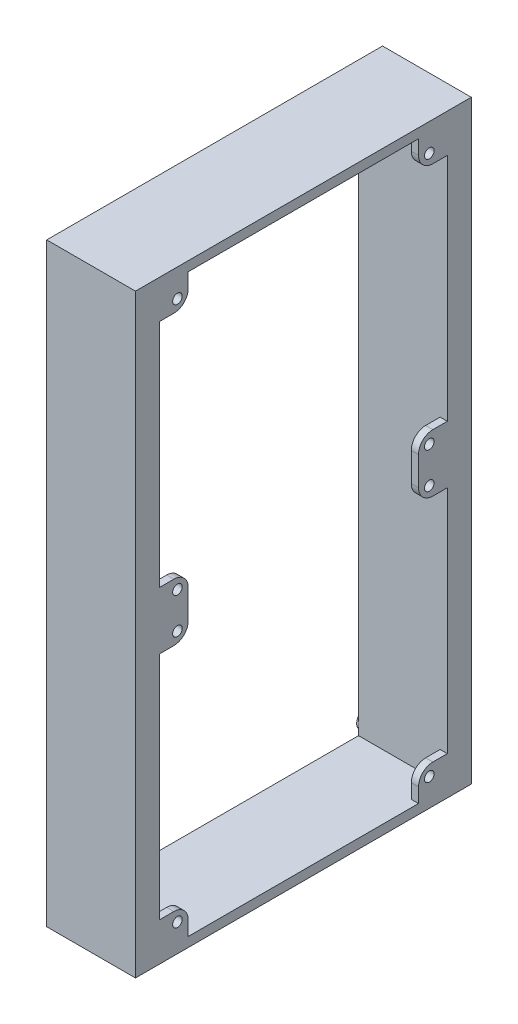
SolidWorks part; units mm, degrees
ref_plane "Front Plane" through (0, 0, 0) normal (1, 0, 0) x (0, 1, 0)
ref_plane "Top Plane" through (0, 0, 0) normal (0, 0, 1) x (0, 1, 0)
ref_plane "Right Plane" through (0, 0, 0) normal (0, 1, 0) x (-1, 0, 0)
sketch "Sketch1" plane through (0, 0, 0) normal (1, 0, 0) x (0, 1, 0)
  line L0 (0, 60) -> (0, -60) construction
  line L1 (-120, -60) -> (120, -60)
  line L2 (-120, -60) -> (-120, 60)
  line L3 (-120, 60) -> (120, 60)
  line L4 (120, -60) -> (120, 60)
  line L5 (-120, -60) -> (120, 60) construction
  line L6 (-120, 60) -> (120, -60) construction
  line L7 (0, 60) -> (0, -60.0055) construction
  line L8 (-120, -60) -> (0, 60) construction
  line L9 (-12, 60) -> (0, 60)
  line L10 (-120, 48) -> (-114, 48)
  line L11 (-120, 48) -> (-120, 60)
  line L12 (-120, 60) -> (-108, 60)
  line L13 (-108, 54) -> (-108, 60)
  line L14 (-12, 60) -> (-12, 54)
  line L15 (-6, 48) -> (0, 48)
  line L16 (0, 60) -> (0, 48)
  line L17 (0, -48) -> (0, -60)
  line L18 (0, -48) -> (-6, -48)
  line L19 (-12, -54) -> (-12, -60)
  line L20 (0, -60) -> (-12, -60)
  line L21 (-108, -60) -> (-120, -60)
  line L22 (-108, -60) -> (-108, -54)
  line L23 (-114, -48) -> (-120, -48)
  line L24 (-120, -60) -> (-120, -48)
  line L25 (0, 48) -> (0, 60)
  line L26 (0, 48) -> (6, 48)
  line L27 (12, 54) -> (12, 60)
  line L28 (0, 60) -> (12, 60)
  line L29 (12, -60) -> (0, -60)
  line L30 (0, -60) -> (0, -48)
  line L31 (6, -48) -> (0, -48)
  line L32 (12, -60) -> (12, -54)
  line L33 (120, -48) -> (120, -60)
  line L34 (120, -60) -> (108, -60)
  line L35 (108, -54) -> (108, -60)
  line L36 (120, -48) -> (114, -48)
  line L37 (108, 60) -> (120, 60)
  line L38 (120, 60) -> (120, 48)
  line L39 (114, 48) -> (120, 48)
  line L40 (108, 60) -> (108, 54)
  line L59 (-124, 70) -> (124, 70)
  line L60 (-124, 70) -> (-124, -70)
  line L61 (-124, -70) -> (124, -70)
  line L62 (124, 70) -> (124, -70)
  line L63 (-124, 70) -> (124, -70) construction
  line L64 (-124, -70) -> (124, 70) construction
  circle A0 centre (-112.5, 52.5) radius 2
  arc A1 (-114, 48) -> (-108, 54) centre (-114, 54) ccw
  arc A2 (-12, 54) -> (-6, 48) centre (-6, 54) ccw
  circle A3 centre (-7.5, 52.5) radius 2
  arc A4 (-6, -48) -> (-12, -54) centre (-6, -54) ccw
  circle A5 centre (-7.5, -52.5) radius 2
  arc A6 (-108, -54) -> (-114, -48) centre (-114, -54) ccw
  circle A7 centre (-112.5, -52.5) radius 2
  arc A8 (6, 48) -> (12, 54) centre (6, 54) ccw
  circle A9 centre (7.5, 52.5) radius 2
  circle A10 centre (7.5, -52.5) radius 2
  arc A11 (12, -54) -> (6, -48) centre (6, -54) ccw
  arc A12 (114, -48) -> (108, -54) centre (114, -54) ccw
  circle A13 centre (112.5, -52.5) radius 2
  arc A14 (108, 54) -> (114, 48) centre (114, 54) ccw
  circle A15 centre (112.5, 52.5) radius 2
  point P0 (0, 0)
  point P12 (0, 0)
  point P16 (-60, 0)
  point P18 (-117, 48)
  point P19 (-108, 57)
  point P22 (-108, 48)
  point P24 (0, 0)
  dimension "D3" = 4
  dimension "D5" = 105
  dimension "D8" = 6
  dimension "D1" = 240
  dimension "D2" = 120
  dimension "D4" = 7.5
  dimension "D6" = 120
  dimension "D7" = 12
  dimension "D9" = 120
  dimension "D10" = 4
  dimension "D11" = 2
  dimension "D12" = 248
  dimension "D13" = 140
extrude "Boss-Extrude2" add sketch "Sketch1" along normal blind 3 contours L10 A1 L13 L3 L2 A0 | L62 L59 L60 L61 L4 L1 L2 L3 | L14 A2 L15 L16 L3 A3 | L26 A8 L27 L3 L16 A9 | L40 A14 L39 L4 L3 A15 | L36 A12 L35 L1 L4 A13 | L32 A11 L31 L17 L1 A10 | L18 A4 L19 L1 L17 A5 | L22 A6 L23 L2 L1 A7 region at (0, -114.4434, -54.4434) region at (0, -5.5566, -54.4434) region at (0, -114.4434, 54.4434) region at (0, 5.5566, -54.4434) region at (0, 114.4434, -54.4434) region at (0, -5.5566, 54.4434) region at (0, 5.5566, 54.4434) region at (0, 114.4434, 54.4434) region at (0, 0, 67.1521)
extrude "Boss-Extrude5" add sketch "Sketch1<6>" against normal blind 34 contours L62 L59 L60 L61 L4 L1 L2 L3 region at (0, 0, 67.1521)
sketch "Sketch1<6>" plane through (0, 0, 0) normal (1, 0, 0) x (0, 1, 0) same geometry as "Sketch1"
sketch "Sketch14" plane through (-34, 0, 0) normal (-1, 0, 0) x (0, -1, 0)
  line L1 (0, 0) -> (-50000, 0) construction
  line L2 (-124, 70) -> (-124, -70) construction
  line L3 (0, 0) -> (0, -50000) construction
  line L4 (120, -60) -> (-120, -60) construction
  line L5 (124, 70) -> (-124, 70) construction
  line L6 (-123, 69) -> (123, 69)
  line L7 (-123, 69) -> (-123, -69)
  line L8 (-123, -69) -> (123, -69)
  line L9 (123, 69) -> (123, -69)
  line L10 (-122.6, 68.6) -> (122.6, 68.6)
  line L11 (122.6, 68.6) -> (122.6, -68.6)
  line L12 (-122.6, -68.6) -> (122.6, -68.6)
  line L13 (-122.6, 68.6) -> (-122.6, -68.6)
  line L14 (124, 70) -> (124, -70) construction
  line L15 (124, -70) -> (-124, -70) construction
  line L17 (120, 60) -> (-120, 60) construction
  circle A0 centre (-116.0377, 63.95) radius 3.15
  circle A1 centre (-116.0377, 63.95) radius 3.95
  circle A2 centre (116.0377, 63.95) radius 3.15
  circle A3 centre (116.0377, 63.95) radius 3.95
  circle A4 centre (116.0377, -63.95) radius 3.15
  circle A5 centre (116.0377, -63.95) radius 3.95
  circle A6 centre (-116.0377, -63.95) radius 3.95
  circle A7 centre (-116.0377, -63.95) radius 3.15
  point P13 (-124, 0)
  point P18 (0, -60)
  dimension "D1" = 6.3
  dimension "D8" = 3.95
  dimension "D3" = 1
  dimension "D4" = 0.4
  dimension "D5" = 1
  dimension "D6" = 1
  dimension "D7" = 1
  dimension "D2" = 0.8
extrude "Boss-Extrude7" add sketch "Sketch14" along normal blind 0.2 contours L7 L8 L9 L6 | L13 L12 L11 L10
extrude "Boss-Extrude9" add sketch "Sketch14<4>" along normal blind 0.8 contours A1 | A3 | A5 | A6
sketch "Sketch14<4>" plane through (-34, 0, 0) normal (-1, 0, 0) x (0, -1, 0) same geometry as "Sketch14"
extrude "Mounting magnet holes" cut sketch "Sketch14<5>" along normal blind 0.8 and the other way blind 1.2 contours A0 | A7 | A4 | A2
sketch "Sketch14<5>" plane through (-34, 0, 0) normal (-1, 0, 0) x (0, -1, 0) same geometry as "Sketch14"
sketch "Sketch17" plane through (-34.2, 0, 0) normal (-1, 0, 0) x (0, -1, 0)
  line L10 (-122.6, 68.6) -> (122.6, 68.6)
  line L11 (-122.6, 68.6) -> (-122.6, -68.6)
  line L12 (123.2, 69.2) -> (-123.2, 69.2)
  line L13 (-123.2, 69.2) -> (-123.2, -69.2)
  line L14 (-123.2, -69.2) -> (123.2, -69.2)
  line L15 (123.2, -69.2) -> (123.2, 69.2)
  line L16 (123.2, 69.2) -> (-123.2, 69.2)
  line L17 (-123.2, 69.2) -> (-123.2, -69.2)
  line L18 (-123.2, -69.2) -> (123.2, -69.2)
  line L19 (123.2, -69.2) -> (123.2, 69.2)
  line L20 (-122.6, -68.6) -> (122.6, -68.6)
  line L21 (122.6, 68.6) -> (122.6, -68.6)
  dimension "D1" = 0.2
extrude "Boss-Extrude10" add sketch "Sketch17" along normal blind 0.4
chamfer "Chamfer1" distance 0.4 angle 30 4 edges at (-34.6, 0, -69.2) (-34.6, -123.2, 0) (-34.6, 123.2, 0) (-34.6, 0, 69.2) first distance on face at (-34.4, 0, -69.2) first distance on face at (-34.4, -123.2, 0) first distance on face at (-34.4, 123.2, 0) first distance on face at (-34.4, 0, 69.2)
sketch "Sketch18" plane through (3, 0, 0) normal (1, 0, 0) x (0, 1, 0)
  line L0 (-124, 70) -> (124, 70) construction
  line L1 (-124, 70) -> (-124, -70) construction
  line L2 (0, 0) -> (-358.4227, 0) construction
  line L3 (0, 0) -> (0, 85.8788) construction
  circle A0 centre (-119, 65) radius 3.15
  circle A2 centre (119, 65) radius 3.15
  circle A4 centre (119, -65) radius 3.15
  circle A7 centre (-119, -65) radius 3.15
  dimension "D1" = 6.3
  dimension "D2" = 5
  dimension "D3" = 5
  dimension "D4" = 6.3
extrude "Cover magnet holes" cut sketch "Sketch18" against normal blind 2.2 from offset 0.4 offset against normal yes
sketch "Sketch19" plane through (0, 0, 60) normal (0, 0, -1) x (1, 0, 0)
  line L0 (-34, -120) -> (0, -120) construction
  line L1 (-13, -120) -> (-29, -120)
  line L2 (-13, -120) -> (-13, 120)
  line L3 (-13, 120) -> (-29, 120)
  line L4 (-29, -120) -> (-29, 120)
  line L5 (-34, 120) -> (0, 120) construction
  line L7 (0, -108) -> (0, -120) construction
  dimension "D1" = 29
  dimension "D2" = 16
extrude "Cut-Extrude1" cut sketch "Sketch19" against normal blind 5
chamfer "Chamfer2" distance 3 angle 60 1 edges at (-29, 0, 60) first distance on face at (-32.3333, 0, 60)
chamfer "Chamfer3" distance 5 angle 45 1 edges at (-13, 0, 60)
sketch "Sketch20" plane through (0, -120, 0) normal (0, 1, 0) x (-1, 0, 0)
  line L0 (8, 60) -> (13, 65)
  line L1 (13, 65) -> (29.1132, 65)
  line L2 (29.1132, 65) -> (32, 60)
  line L4 (8, 60) -> (0, 60) construction
  line L5 (29.1132, 55) -> (32, 60)
  line L6 (13, 55) -> (29.1132, 55)
  line L7 (8, 60) -> (13, 55)
extrude "Cut-Extrude2" cut sketch "Sketch20" against normal through all contours L7 L6 L5 L2 L1 L0
